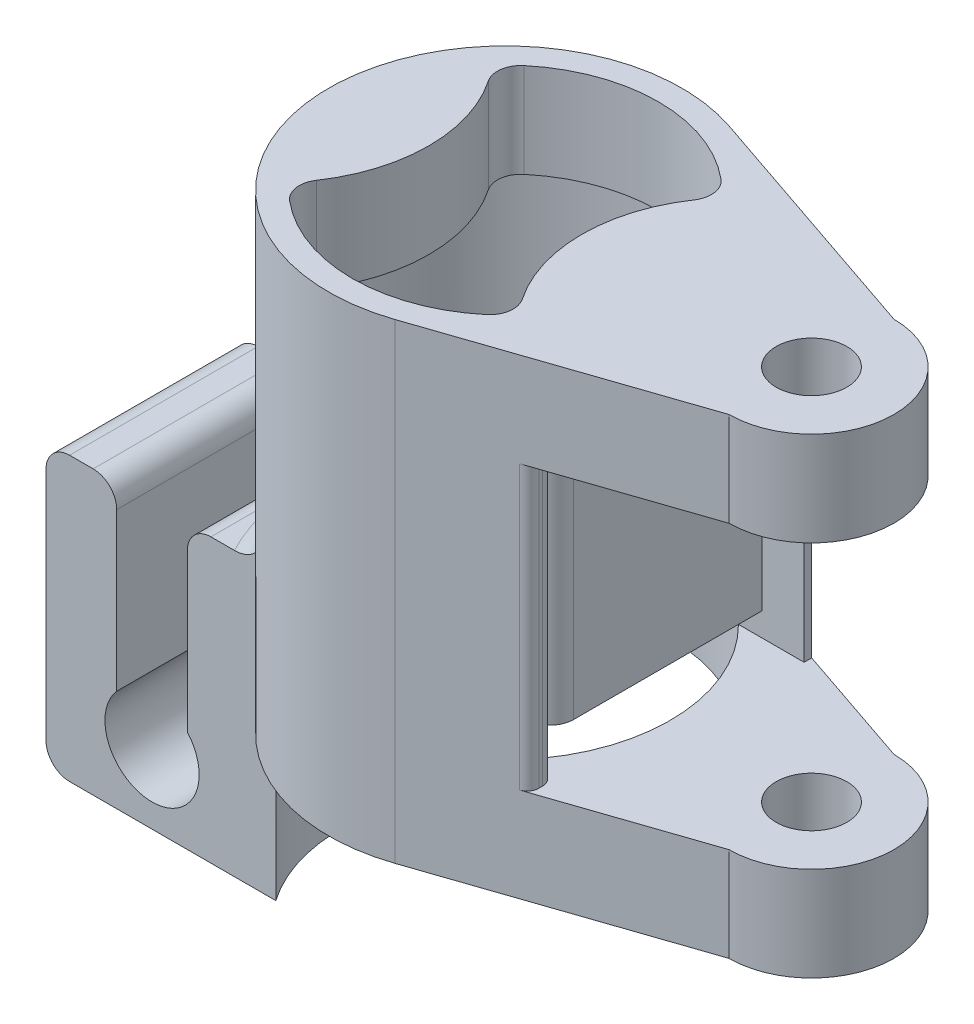
SolidWorks part; units mm, degrees
material "Rubber"
ref_plane "Front Plane" through (0, 0, 0) normal (0, 0, 1) x (1, 0, 0)
ref_plane "Top Plane" through (0, 0, 0) normal (0, 1, 0) x (1, 0, 0)
ref_plane "Right Plane" through (0, 0, 0) normal (1, 0, 0) x (0, 0, -1)
sketch "Sketch1" plane through (0, 0, 0) normal (0, 1, 0) x (1, 0, 0)
  line L1 (13.0007, -3.5021) -> (2.4139, -7.1009)
  line L2 (13.0007, 3.5021) -> (2.4139, 7.1009)
  arc A0 (2.4139, 7.1009) -> (2.4139, -7.1009) centre (0, 0) ccw
  circle A1 centre (13.0007, 0) radius 1.5
  arc A2 (13.0007, -3.5021) -> (13.0007, 3.5021) centre (13.0007, 0) ccw
  arc A14 (4.1856, 4.973) -> (-4.1856, 4.973) centre (0, 0) ccw
  arc A20 (-4.1856, -4.973) -> (4.1856, -4.973) centre (0, 0) ccw
  arc A21 (-4.3694, -3.6469) -> (-4.3694, 3.6469) centre (-9.75, 0) ccw
  arc A24 (4.3694, 3.6469) -> (4.3694, -3.6469) centre (9.75, 0) ccw
  arc A25 (-4.1856, 4.973) -> (-4.3694, 3.6469) centre (-3.5417, 4.2079) ccw
  arc A26 (-4.1856, -4.973) -> (-4.3694, -3.6469) centre (-3.5417, -4.2079) cw
  arc A27 (4.3694, -3.6469) -> (4.1856, -4.973) centre (3.5417, -4.2079) cw
  arc A28 (4.1856, 4.973) -> (4.3694, 3.6469) centre (3.5417, 4.2079) cw
  dimension "D1" = 1
extrude "Boss-Extrude1" add sketch "Sketch1" along normal blind 20
ref_plane "Plane1" through (0, 0, 10) normal (0, 0, 1) x (1, 0, 0)
sketch "Sketch3" plane through (0, 0, 10) normal (0, 0, 1) x (1, 0, 0)
  line L0 (16.5028, 20) -> (16.5028, 16)
  line L1 (16.5028, 0) -> (16.5028, 20) construction
  line L2 (16.5028, 0) -> (16.5028, 4)
  line L3 (7.7073, 20) -> (7.7073, 16)
  line L4 (2.4139, 20) -> (13.0007, 20) construction
  line L5 (7.7073, 0) -> (7.7073, 4)
  line L6 (2.4139, 0) -> (13.0007, 0) construction
  line L7 (7.7073, 4) -> (16.5028, 4)
  line L8 (16.5028, 16) -> (16.5028, 4)
  line L9 (7.7073, 16) -> (7.7073, 4)
  line L10 (16.5028, 16) -> (7.7073, 16)
extrude "Cut-Extrude1" cut sketch "Sketch3" against normal blind 20 contours L8 L10 L9 L7 region at (12.105, 10, 10)
sketch "Sketch4" plane through (7.7073, 0, 0) normal (1, 0, 0) x (0, 0, -1)
  line L0 (5.3015, 4) -> (-5.3015, 4) construction
  line L1 (4.9802, 16) -> (-4.6198, 16)
  line L2 (4.9802, 16) -> (4.9802, 4)
  line L3 (4.9802, 4) -> (-4.6198, 4)
  line L4 (-4.6198, 16) -> (-4.6198, 4)
  line L5 (4.9802, 16) -> (-4.6198, 4) construction
  line L6 (4.9802, 4) -> (-4.6198, 16) construction
  point P0 (0.1802, 10)
extrude "Cut-Extrude2" cut sketch "Sketch4" against normal blind 7
sketch "Sketch5" plane through (0, 0, 0) normal (0, -1, 0) x (1, 0, 0)
  circle A0 centre (0, 0) radius 7
extrude "Cut-Extrude3" cut sketch "Sketch5" against normal blind 16
sketch "Sketch6" plane through (7.7073, 0, 0) normal (1, 0, 0) x (0, 0, -1)
  line L4 (-5.9607, 4) -> (-3.9607, 4)
  line L6 (4.9802, 4) -> (-4.6198, 4) construction
  line L7 (-5.9607, 16) -> (-3.9607, 16)
  line L9 (-7, 16) -> (7, 16) construction
  line L10 (-5.9607, 16) -> (-5.9607, 4)
  line L11 (-3.9607, 4) -> (-3.9607, 16)
  point P5 (-4.9607, 4)
  point P12 (-4.9607, 16)
extrude "Cut-Extrude4" cut sketch "Sketch6" against normal blind 1
fillet "Fillet1" radius 0.5 2 edges at (6.7073, 10, 4.6198) (6.7073, 10, 5.6414)
sketch "Sketch7" plane through (0, 0, -4.9802) normal (0, 0, 1) x (1, 0, 0)
  line L7 (4.4191, 15) -> (4.4191, 5)
  line L12 (5.4191, 15) -> (4.4191, 15)
  line L14 (4.4191, 5) -> (5.4191, 5)
  line L15 (5.4191, 15) -> (5.9191, 15)
  line L16 (5.9191, 15) -> (5.9191, 5)
  line L17 (5.9191, 5) -> (5.4191, 5)
extrude "Boss-Extrude3" add sketch "Sketch7" along normal blind 9 and the other way up to surface other way up to face at (0, 0, -7)
fillet "Fillet2" radius 1 2 edges at (4.4191, 10, 4.0198) (5.9191, 10, 4.0198)
sketch "Sketch8" plane through (0, 0, 0) normal (0, -1, 0) x (1, 0, 0)
  line L0 (-9.5, 4) -> (-5.7446, 4)
  line L1 (-9.5, 4) -> (-9.5, -4)
  line L2 (-9.5, -4) -> (-5.7446, -4)
  arc A0 (-5.7446, 4) -> (-5.7446, -4) centre (0, 0) ccw
  point P12 (-9.5, 0)
extrude "Boss-Extrude4" add sketch "Sketch8" along normal blind 7 and the other way blind 5
sketch "Sketch9" plane through (0, 0, -4) normal (0, 0, -1) x (-1, 0, 0)
  line L0 (9.5, -7) -> (12.5, -7)
  line L1 (12.5, -7) -> (15.5, -7)
  line L2 (15.5, -7) -> (15.5, 5)
  line L3 (15.5, 5) -> (12.5, 5)
  line L4 (12.5, 5) -> (12.5, -4)
  line L5 (12.5, -4) -> (9.5, -4)
  line L6 (9.5, 5) -> (9.5, -7) construction
  line L7 (9.5, -4) -> (9.5, -7)
extrude "Boss-Extrude5" add sketch "Sketch9" against normal blind 8
sketch "Sketch10" plane through (0, 0, -4) normal (0, 0, -1) x (-1, 0, 0)
  line L0 (12.5, -4) -> (9.5, -4) construction
  circle A0 centre (11, -4) radius 2
extrude "Cut-Extrude5" cut sketch "Sketch10" against normal blind 13
fillet "Fillet3" radius 1 5 edges at (-7.5, 5, 0) (-9.5, 5, 0) (-12.5, 5, 0) (-15.5, 5, 0) (-15.5, -7, 0)
